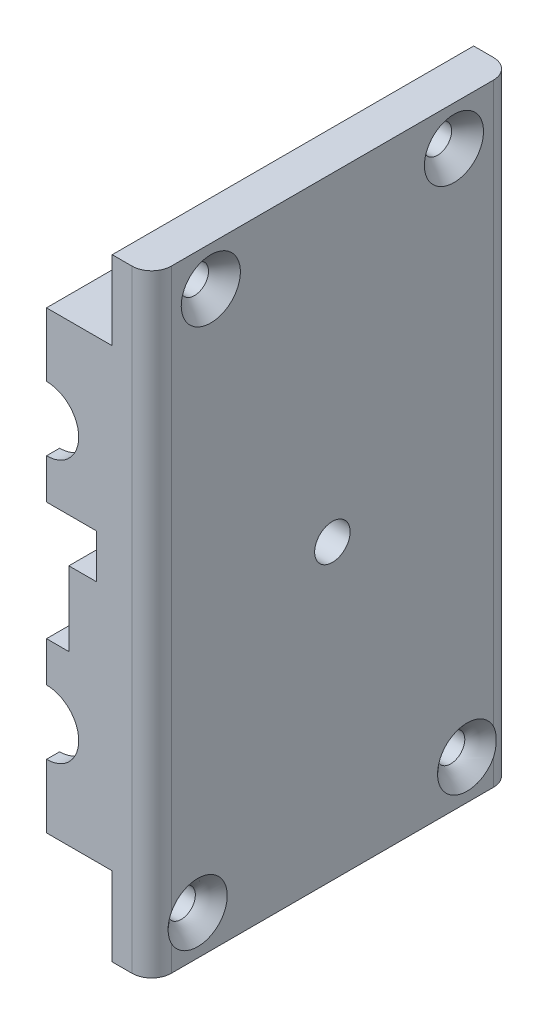
SolidWorks part; units mm, degrees
ref_plane "Front Plane" through (0, 0, 0) normal (0, 0, 1) x (1, 0, 0)
ref_plane "Top Plane" through (0, 0, 0) normal (0, 1, 0) x (1, 0, 0)
ref_plane "Right Plane" through (0, 0, 0) normal (1, 0, 0) x (0, 0, -1)
sketch "Sketch1" plane through (0, 0, 0) normal (0, 0, 1) x (1, 0, 0)
  line L0 (0, 0) -> (0, -93.2)
  line L1 (0, -93.2) -> (-6, -93.2)
  line L2 (-6, -93.2) -> (-6, -81.2)
  line L3 (-6, -81.2) -> (-16, -81.2)
  line L4 (-16, -81.2) -> (-16, -74.2)
  line L5 (-16, -59) -> (-16, -44.3)
  line L6 (-16, -44.3) -> (-8.4, -44.3)
  line L7 (-8.4, -44.3) -> (-8.4, -37.6)
  line L8 (-8.4, -37.6) -> (-16, -37.6)
  line L9 (-16, -37.6) -> (-16, -34.2)
  line L10 (-16, -19) -> (-16, -12)
  line L11 (-16, -12) -> (-6, -12)
  line L12 (-6, -12) -> (-6, 0)
  line L13 (-6, 0) -> (0, 0)
  arc A0 (-16, -74.2) -> (-16, -59) centre (-16, -66.6) ccw
  arc A1 (-16, -34.2) -> (-16, -19) centre (-16, -26.6) ccw
  dimension "D6" = 7.6
  dimension "D7" = 7.6
  dimension "D1" = 6
  dimension "D2" = 12
  dimension "D3" = 12
  dimension "D4" = 14.7
  dimension "D5" = 40
  dimension "D8" = 7
  dimension "D9" = 3.4
  dimension "D11" = 10
  dimension "D12" = 10
extrude "Boss-Extrude1" add sketch "Sketch1" along normal blind 55
ref_plane "Plane1" through (0, 0, 28.5) normal (0, 0, -1) x (-1, 0, 0)
sketch "Sketch2" plane through (0, 0, 28.5) normal (0, 0, -1) x (-1, 0, 0)
  line L0 (16, -34.2) -> (16, -31.5)
  line L1 (16, -21.7) -> (16, -19)
  arc A0 (16, -19) -> (16, -34.2) centre (16, -26.6) ccw
  arc A1 (16, -21.7) -> (16, -31.5) centre (16, -26.6) ccw
  dimension "D1" = 4.9
extrude "Boss-Extrude2" add sketch "Sketch2" along normal blind 2
sketch "Sketch3" plane through (0, 0, 28.5) normal (0, 0, -1) x (-1, 0, 0)
  line L0 (16, -74.2) -> (16, -71.5)
  line L1 (16, -61.7) -> (16, -59)
  arc A0 (16, -59) -> (16, -74.2) centre (16, -66.6) ccw
  arc A1 (16, -61.7) -> (16, -71.5) centre (16, -66.6) ccw
  dimension "D1" = 4.9
extrude "Boss-Extrude3" add sketch "Sketch3" along normal blind 2
ref_plane "Plane2" through (0, 0, 2) normal (0, 0, -1) x (-1, 0, 0)
sketch "Sketch4" plane through (0, 0, 2) normal (0, 0, -1) x (-1, 0, 0)
  line L1 (16, -59) -> (16, -61.7)
  line L2 (16, -74.2) -> (16, -81.2) construction
  line L4 (16, -71.5) -> (16, -74.2)
  line L5 (16, -19) -> (16, -21.7)
  line L6 (16, -31.5) -> (16, -34.2)
  arc A1 (16, -59) -> (16, -74.2) centre (16, -66.6) ccw construction
  arc A2 (16, -74.2) -> (16, -59) centre (16, -66.6) cw
  arc A4 (16, -61.7) -> (16, -71.5) centre (16, -66.6) ccw
  arc A5 (16, -34.2) -> (16, -19) centre (16, -26.6) cw
  arc A6 (16, -21.7) -> (16, -31.5) centre (16, -26.6) ccw
  dimension "D1" = 4.9
  dimension "D2" = 4.9
extrude "Boss-Extrude5" add sketch "Sketch4" along normal blind 2
ref_plane "Plane3" through (0, 0, 53) normal (0, 0, -1) x (-1, 0, 0)
sketch "Sketch5" plane through (0, 0, 53) normal (0, 0, -1) x (-1, 0, 0)
  line L0 (16, -19) -> (16, -21.7)
  line L1 (16, -31.5) -> (16, -34.2)
  line L2 (16, -59) -> (16, -61.7)
  line L3 (16, -71.5) -> (16, -74.2)
  arc A0 (16, -19) -> (16, -34.2) centre (16, -26.6) ccw construction
  arc A1 (16, -34.2) -> (16, -19) centre (16, -26.6) cw
  arc A2 (16, -21.7) -> (16, -31.5) centre (16, -26.6) ccw
  arc A3 (16, -74.2) -> (16, -59) centre (16, -66.6) cw
  arc A4 (16, -61.7) -> (16, -71.5) centre (16, -66.6) ccw
  dimension "D1" = 4.9
extrude "Boss-Extrude6" add sketch "Sketch5" against normal blind 2
sketch "Sketch7" plane through (0, 0, 55) normal (0, 0, 1) x (1, 0, 0)
  line L1 (-16, -44.3) -> (-12.6, -44.3)
  line L2 (-16, -44.3) -> (-16, -55.6)
  line L3 (-16, -55.6) -> (-12.6, -55.6)
  line L4 (-12.6, -44.3) -> (-12.6, -55.6)
  dimension "D1" = 3.4
  dimension "D2" = 11.3
extrude "Cut-Extrude2" cut sketch "Sketch7" against normal up to surface (55 mm away) up to face at (-9.9375, -45.1875, 0)
sketch "Sketch8" plane through (0, 0, 0) normal (1, 0, 0) x (0, 0, -1)
  line L0 (-55, -93.2) -> (-55, 0) construction
  line L1 (0, -93.2) -> (0, 0) construction
  line L2 (-55, 0) -> (0, 0) construction
  line L3 (-55, -93.2) -> (0, -93.2) construction
  circle A0 centre (-46, -6) radius 2.15
  circle A1 centre (-9, -6) radius 2.15
  circle A2 centre (-7, -87.2) radius 2.15
  circle A3 centre (-48, -87.2) radius 2.15
  dimension "D1" = 4.3
  dimension "D2" = 4.3
  dimension "D3" = 4.3
  dimension "D4" = 4.3
  dimension "D5" = 9
  dimension "D6" = 9
  dimension "D7" = 7
  dimension "D8" = 7
  dimension "D9" = 6
  dimension "D10" = 6
  dimension "D11" = 6
  dimension "D12" = 6
extrude "Cut-Extrude3" cut sketch "Sketch8" against normal up to surface (6 mm away) up to face at (-6, -6, 27.5)
sketch "Sketch9" plane through (0, 0, 0) normal (1, 0, 0) x (0, 0, -1)
  line L0 (-55, 0) -> (0, 0) construction
  line L1 (-55, -93.2) -> (-55, 0) construction
  circle A0 centre (-27.5, -48.6) radius 2.7
  dimension "D1" = 5.4
  dimension "D2" = 48.6
  dimension "D3" = 27.5
extrude "Cut-Extrude4" cut sketch "Sketch9" against normal up to surface (12.6 mm away) up to face at (-12.6, -49.95, 27.5)
ref_plane "Plane4" through (-2.5, 0, 0) normal (1, 0, 0) x (0, 0, -1)
sketch "Sketch12" plane through (-2.5, 0, 0) normal (1, 0, 0) x (0, 0, -1)
  circle A0 centre (-46, -6) radius 2.15 construction
  circle A1 centre (-46, -6) radius 2.15
sketch "Sketch13" plane through (0, 0, 0) normal (1, 0, 0) x (0, 0, -1)
  circle A0 centre (-46, -6) radius 4.5
  dimension "D1" = 9
loft "Cut-Loft1" cut profiles "Sketch13", "Sketch12" connector at (0, -9.0908, 49.2707) connector at (-2.5, -7.7977, 47.1793)
pattern_linear "LPattern1" count 2 spacing 37 along (0, 0, -1) of "Cut-Loft1"
sketch "Sketch14" plane through (-2.5, 0, 0) normal (1, 0, 0) x (0, 0, -1)
  circle A0 centre (-48, -87.2) radius 2.15 construction
  circle A1 centre (-48, -87.2) radius 2.15
sketch "Sketch15" plane through (0, 0, 0) normal (1, 0, 0) x (0, 0, -1)
  circle A0 centre (-48, -87.2) radius 4.5
  dimension "D1" = 9
loft "Cut-Loft2" cut profiles "Sketch14", "Sketch15" connector at (-2.5, -88.8038, 46.5681) connector at (0, -88.245, 43.623)
pattern_linear "LPattern2" count 2 spacing 41 along (0, 0, -1) of "Cut-Loft2"
fillet "Fillet1" radius 3 2 edges at (0, -46.6, 0) (0, -46.6, 55)
